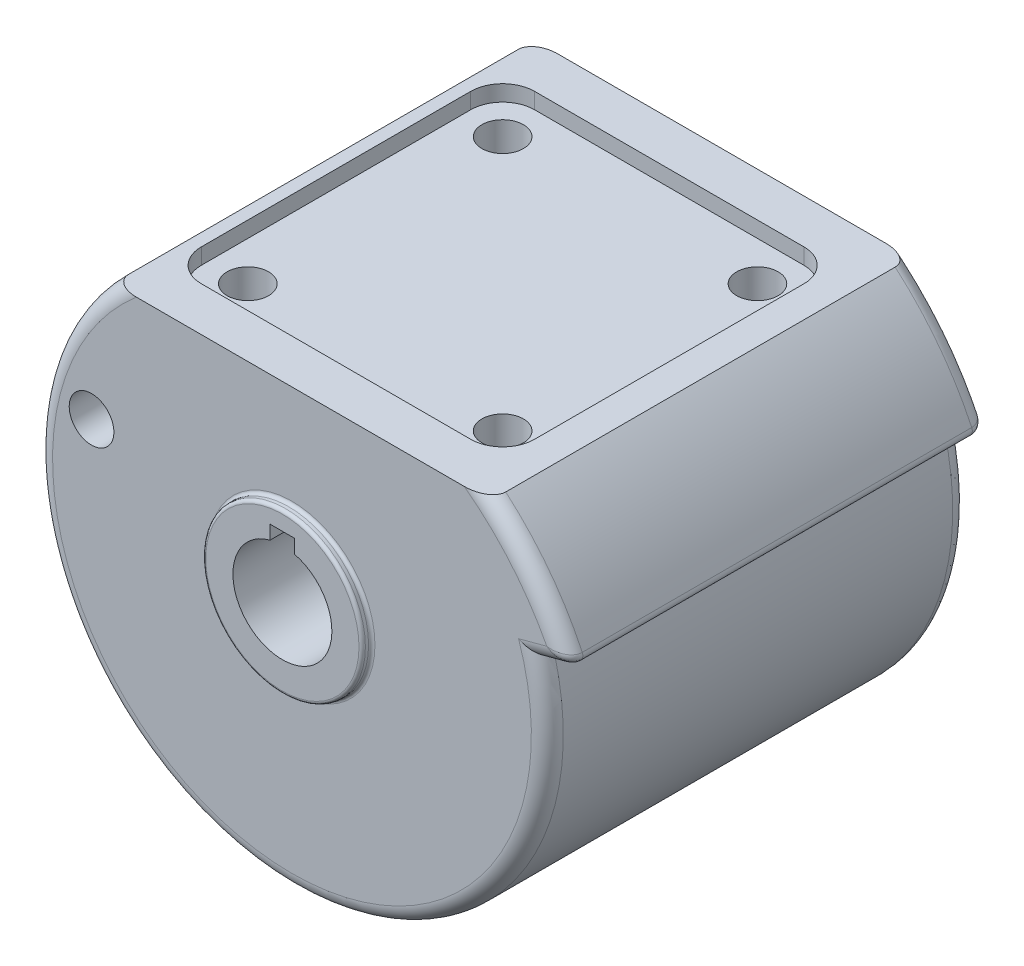
SolidWorks part; units mm, degrees
ref_plane "Front Plane" through (0, 0, 0) normal (0, 0, 1) x (1, 0, 0)
ref_plane "Top Plane" through (0, 0, 0) normal (0, 1, 0) x (1, 0, 0)
ref_plane "Right Plane" through (0, 0, 0) normal (1, 0, 0) x (0, 0, -1)
sketch "Sketch1" plane through (0, 0, 0) normal (0, 0, 1) x (1, 0, 0)
  circle A0 centre (0, 0) radius 40
  dimension "D1" = 80
extrude "Boss-Extrude1" add sketch "Sketch1" along normal blind 66
sketch "Sketch4" plane through (0, 0, 0) normal (0, 0, -1) x (-1, 0, 0)
  line L0 (0, 0) -> (0, 40) construction
  line L1 (0, 0) -> (-43.4667, 11.6469)
  line L4 (0, 0) -> (43.3013, 25) construction
  line L5 (0, 0) -> (0, 40)
  circle A0 centre (0, 0) radius 40 construction
  arc A1 (-43.4667, 11.6469) -> (0, 40) centre (0, -7.4948) cw
  dimension "D1" = 75
  dimension "D2" = 45
  dimension "D3" = 60
extrude "Boss-Extrude3" add sketch "Sketch4" against normal up to surface (66 mm away) up to face at (40, 0, 66)
fillet "Fillet2" radius 1 1 edges at (43.4667, 11.6469, 33)
fillet "Fillet4" radius 2.5 8 edges at (40.4815, 10.847, 66) (42.9742, 11.8862, 66) (25.4464, 32.608, 66) (-24.3505, -31.7341, 66) (40.4815, 10.847, 0) (42.9742, 11.8862, 0) (25.4464, 32.608, 0) (-24.3505, -31.7341, 0)
sketch "Sketch2" plane through (0, 0, 0) normal (0, 0, -1) x (-1, 0, 0)
  circle A0 centre (0, 0) radius 12.5
  dimension "D1" = 25
extrude "Boss-Extrude2" add sketch "Sketch2" along normal blind 1.5
ref_plane "Plane1" through (0, 0, 33) normal (0, 0, -1) x (-1, 0, 0)
mirror "Mirror1" about plane through (0, 0, 33) normal (0, 0, -1) of "Boss-Extrude2"
sketch "Sketch3" plane through (0, 0, -1.5) normal (0, 0, -1) x (-1, 0, 0)
  circle A0 centre (0, 0) radius 7.75
  dimension "D1" = 15.5
extrude "Cut-Extrude1" cut sketch "Sketch3" against normal up to surface (69 mm away) up to face at (-12.5, 0, 67.5)
fillet "Fillet1" radius 0.5 4 edges at (-12.5, 0, 67.5) (-12.5, 0, -1.5) (12.5, 0, 66) (12.5, 0, 0)
sketch "Sketch5" plane through (0, 0, -1.5) normal (0, 0, -1) x (-1, 0, 0)
  line L1 (-1.925, 9.675) -> (1.925, 9.675)
  line L2 (-1.925, 9.675) -> (-1.925, 5.825)
  line L3 (-1.925, 5.825) -> (1.925, 5.825)
  line L4 (1.925, 9.675) -> (1.925, 5.825)
  line L5 (-1.925, 9.675) -> (1.925, 5.825) construction
  line L6 (-1.925, 5.825) -> (1.925, 9.675) construction
  circle A0 centre (0, 0) radius 7.75 construction
  point P0 (0, 7.75)
  dimension "D1" = 3.85
  dimension "D2" = 3.85
extrude "Cut-Extrude2" cut sketch "Sketch5" against normal up to surface (69 mm away) up to face at (12, 0, 67.5)
sketch "Sketch6" plane through (0, 0, 0) normal (0, 0, -1) x (-1, 0, 0)
  line L0 (31.3926, 8.4116) -> (0, 0) construction
  line L1 (0, 0) -> (0, 37.5) construction
  circle A0 centre (0, 0) radius 40 construction
  circle A1 centre (0, 0) radius 40 construction
  circle A2 centre (31.3926, 8.4116) radius 3.5
  dimension "D1" = 7
  dimension "D2" = 75
  dimension "D3" = 32.5
extrude "Cut-Extrude3" cut sketch "Sketch6" against normal up to surface (66 mm away) up to face at (13, 0, 66)
ref_plane "Plane2" through (0, 28.5, 0) normal (0, 1, 0) x (1, 0, 0)
sketch "Sketch8" plane through (0, 28.5, 0) normal (0, 1, 0) x (1, 0, 0)
  line L0 (0, -63.5) -> (0, -2.5) construction
  line L1 (-40, 7) -> (40, 7)
  line L2 (-40, 7) -> (-40, -73)
  line L3 (-40, -73) -> (40, -73)
  line L4 (40, 7) -> (40, -73)
  line L5 (-40, 7) -> (40, -73) construction
  line L6 (-40, -73) -> (40, 7) construction
  point P0 (0, -33)
  dimension "D1" = 80
  dimension "D2" = 80
extrude "Cut-Extrude4" cut sketch "Sketch8" along normal through all
sketch "Sketch9" plane through (0, 28.5, 0) normal (0, 1, 0) x (1, 0, 0)
  line L0 (36.3, -33) -> (-36.3, -33) construction
  line L1 (-21.1, -59.1) -> (21.1, -59.1)
  line L2 (-26.1, -54.1) -> (-26.1, -11.9)
  line L3 (-21.1, -6.9) -> (21.1, -6.9)
  line L4 (26.1, -54.1) -> (26.1, -11.9)
  line L5 (-26.1, -59.1) -> (26.1, -6.9) construction
  line L6 (-26.1, -6.9) -> (26.1, -59.1) construction
  arc A0 (-21.1, -59.1) -> (-26.1, -54.1) centre (-21.1, -54.1) cw
  arc A1 (21.1, -59.1) -> (26.1, -54.1) centre (21.1, -54.1) ccw
  arc A2 (21.1, -6.9) -> (26.1, -11.9) centre (21.1, -11.9) cw
  arc A3 (-26.1, -11.9) -> (-21.1, -6.9) centre (-21.1, -11.9) cw
  point P0 (0, -33)
  dimension "D3" = 5
  dimension "D1" = 52.2
  dimension "D2" = 52.2
sketch "Sketch15" plane through (0, 0, 0) normal (0, 0, -1) x (-1, 0, 0)
  circle A0 centre (0, 0) radius 40 construction
  arc A3 (-38.637, 10.3528) -> (28.0669, 28.5) centre (0, 0) ccw construction
extrude "Cut-Extrude5" cut sketch "Sketch9" against normal blind 2.5
sketch "Sketch16" plane through (0, 0, 33) normal (0, 0, -1) x (-1, 0, 0)
  line L0 (30.6359, 25.7185) -> (-0.0091, -40)
  line L1 (0, 0) -> (40, 0) construction
  circle A0 centre (0, 0) radius 40 construction
  circle A1 centre (31.3926, 8.4116) radius 3.5 construction
  arc A2 (30.6359, 25.7185) -> (-0.0091, -40) centre (0, 0) cw
  dimension "D2" = 8
  dimension "D1" = 65
extrude "Cut-Extrude6" cut sketch "Sketch16" against normal blind 15 and the other way blind 15
fillet "Fillet5" radius 2.5 2 edges at (-15.3134, -7.1407, 48) (-15.3134, -7.1407, 18)
sketch "Sketch17" plane through (0, 26, 0) normal (0, 1, 0) x (1, 0, 0)
  line L0 (36.3, -33) -> (-36.3, -33) construction
  line L1 (-25.955, -7.045) -> (25.955, -7.045) construction
  line L2 (-25.955, -7.045) -> (-25.955, -58.955) construction
  line L3 (-25.955, -58.955) -> (25.955, -58.955) construction
  line L4 (25.955, -7.045) -> (25.955, -58.955) construction
  line L5 (-25.955, -7.045) -> (25.955, -58.955) construction
  line L6 (-25.955, -58.955) -> (25.955, -7.045) construction
  line L7 (0, -7.045) -> (0, -58.955) construction
  circle A0 centre (-19.955, -13.045) radius 3.25
  circle A1 centre (19.955, -13.045) radius 3.25
  circle A2 centre (19.955, -52.955) radius 3.25
  circle A3 centre (-19.955, -52.955) radius 3.25
  point P0 (0, -33)
  dimension "D3" = 6.5
  dimension "D4" = 6
  dimension "D1" = 51.91
  dimension "D2" = 51.91
extrude "Cut-Extrude7" cut sketch "Sketch17" against normal blind 10
